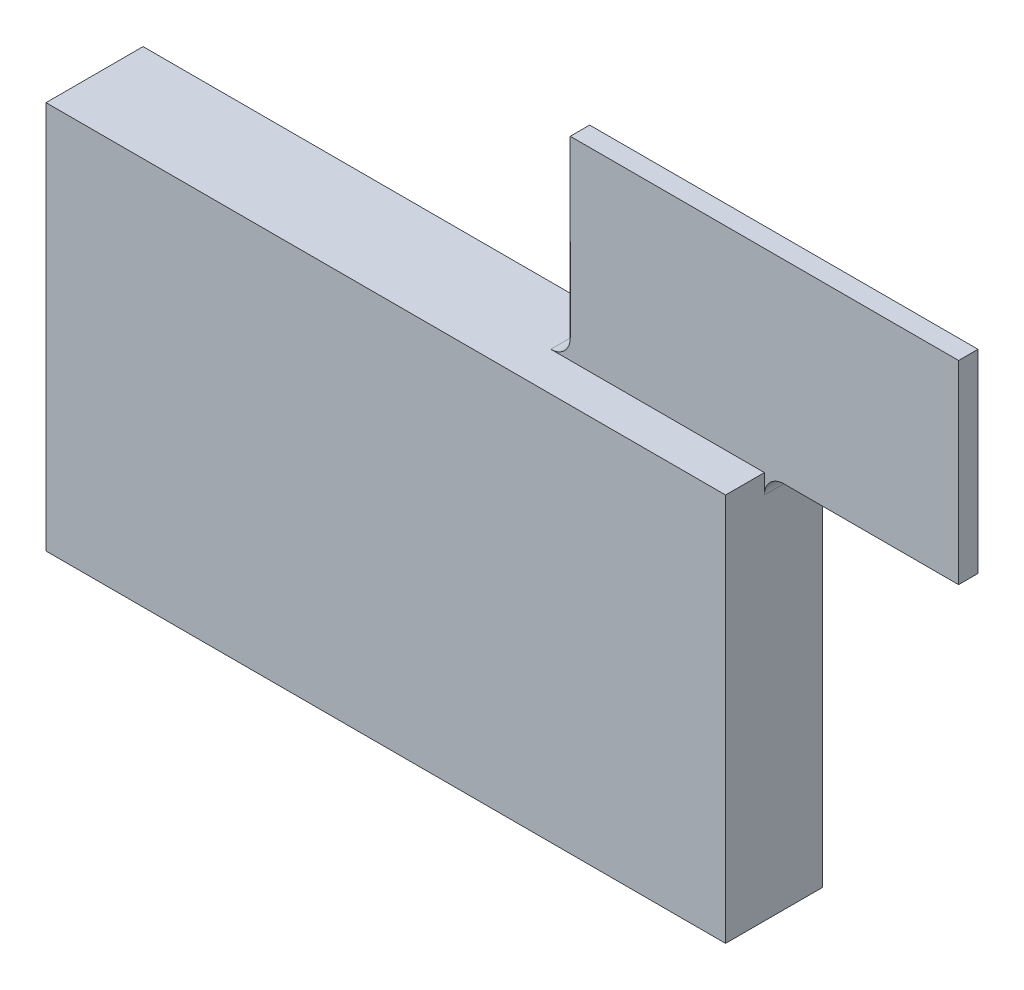
SolidWorks part; units mm, degrees
ref_plane "Plan de face" through (0, 0, 0) normal (0, 0, 1) x (1, 0, 0)
ref_plane "Plan de dessus" through (0, 0, 0) normal (0, 1, 0) x (1, 0, 0)
ref_plane "Plan de droite" through (0, 0, 0) normal (1, 0, 0) x (0, 0, -1)
sketch "Esquisse1" plane through (0, 0, 0) normal (0, 1, 0) x (1, 0, 0)
  line L1 (17.5, -2.5) -> (-17.5, -2.5)
  line L2 (17.5, -2.5) -> (17.5, 2.5)
  line L3 (17.5, 2.5) -> (-17.5, 2.5)
  line L4 (-17.5, -2.5) -> (-17.5, 2.5)
  line L5 (17.5, -2.5) -> (-17.5, 2.5) construction
  line L6 (17.5, 2.5) -> (-17.5, -2.5) construction
  point P0 (0, 0)
  dimension "D1" = 35
  dimension "D2" = 5
extrude "Boss.-Extru.1" add sketch "Esquisse1" along normal blind 20
sketch "Esquisse2" plane through (0, 20, 0) normal (0, 1, 0) x (1, 0, 0)
  line L0 (17.5, -2.5) -> (17.5, 2.5) construction
  line L1 (27.5, -0.5) -> (7.5, -0.5)
  line L2 (27.5, -0.5) -> (27.5, 0.5)
  line L3 (27.5, 0.5) -> (7.5, 0.5)
  line L4 (7.5, -0.5) -> (7.5, 0.5)
  line L5 (27.5, -0.5) -> (7.5, 0.5) construction
  line L6 (27.5, 0.5) -> (7.5, -0.5) construction
  point P0 (17.5, 0)
  dimension "D1" = 20
  dimension "D2" = 1
extrude "Boss.-Extru.2" add sketch "Esquisse2" along normal blind 10
fillet "Congé1" radius 1 2 edges at (7.5, 20, 0) (17.5, 20, 0)
